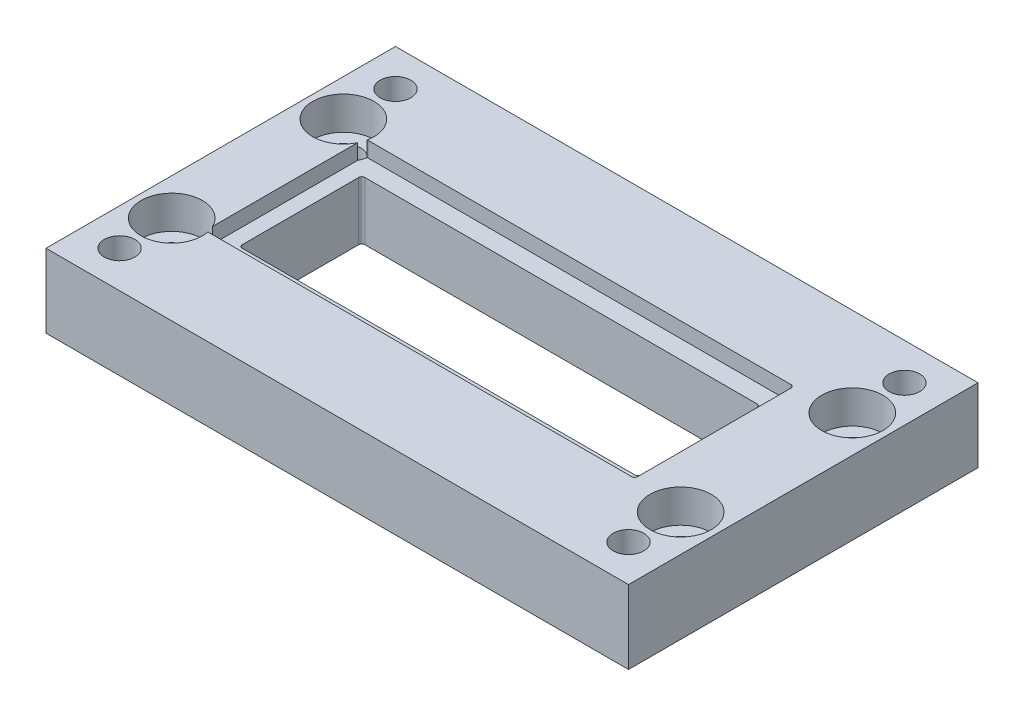
SolidWorks part; units mm, degrees
ref_plane "Front Plane" through (0, 0, 0) normal (0, 0, 1) x (1, 0, 0)
ref_plane "Top Plane" through (0, 0, 0) normal (0, 1, 0) x (1, 0, 0)
ref_plane "Right Plane" through (0, 0, 0) normal (1, 0, 0) x (0, 0, -1)
sketch "Sketch1" plane through (0, 0, 0) normal (0, 1, 0) x (1, 0, 0)
  line L0 (-56.5547, 0) -> (57.1484, 0) construction
  line L1 (47.5, 28.5) -> (-47.5, 28.5)
  line L2 (47.5, 28.5) -> (47.5, -28.5)
  line L3 (47.5, -28.5) -> (-47.5, -28.5)
  line L4 (-47.5, 28.5) -> (-47.5, -28.5)
  line L5 (47.5, 28.5) -> (-47.5, -28.5) construction
  line L6 (47.5, -28.5) -> (-47.5, 28.5) construction
  line L8 (30, -10) -> (-34, -10)
  line L9 (30.5, -9.5) -> (30.5, 9.5)
  line L10 (30, 10) -> (-34, 10)
  line L11 (-34.5, -9.5) -> (-34.5, 9.5)
  line L12 (30.5, -10) -> (-34.5, 10) construction
  line L13 (30.5, 10) -> (-34.5, -10) construction
  line L14 (32.5, 13) -> (-36.5, 13)
  line L15 (33, 12.5) -> (33, -12.5)
  line L16 (32.5, -13) -> (-36.5, -13)
  line L17 (-37, 12.5) -> (-37, -12.5)
  line L18 (33, 13) -> (-37, -13) construction
  line L19 (33, -13) -> (-37, 13) construction
  arc A0 (32.5, -13) -> (33, -12.5) centre (32.5, -12.5) ccw
  arc A1 (32.5, 13) -> (33, 12.5) centre (32.5, 12.5) cw
  arc A2 (-36.5, -13) -> (-37, -12.5) centre (-36.5, -12.5) cw
  arc A3 (-37, 12.5) -> (-36.5, 13) centre (-36.5, 12.5) cw
  arc A4 (-34, -10) -> (-34.5, -9.5) centre (-34, -9.5) cw
  arc A5 (-34, 10) -> (-34.5, 9.5) centre (-34, 9.5) ccw
  arc A6 (30.5, 9.5) -> (30, 10) centre (30, 9.5) ccw
  arc A7 (30, -10) -> (30.5, -9.5) centre (30, -9.5) ccw
  circle A8 centre (-41.5, -22.5) radius 2.058
  circle A9 centre (41.5, -22.5) radius 2.058
  circle A10 centre (-41.5, 22.5) radius 2.058
  circle A11 centre (41.5, 22.5) radius 2.058
  point P0 (0, 0)
  point P8 (-2, 0)
  point P15 (-2, 0)
  dimension "D9" = 0.5
  dimension "D10" = 0.5
  dimension "D11" = 6
  dimension "D13" = 45
  dimension "D1" = 95
  dimension "D2" = 57
  dimension "D3" = 65
  dimension "D4" = 20
  dimension "D5" = 13
  dimension "D6" = 3
  dimension "D7" = 2.5
  dimension "D8" = 26
  dimension "D12" = 83
  dimension "D14" = 6
extrude "Boss-Extrude2" add sketch "Sketch1" along normal blind 12 contours L1 L4 L3 L2 A11 A10 A9 A8 L17 A3 L14 A1 L15 A0 L16 A2 region at (46.3921, 0, 0)
extrude "Boss-Extrude3" add sketch "Sketch1<5>" along normal blind 9.5 contours A3 L17 A2 L16 A0 L15 A1 L14 A7 L8 A4 L11 A5 L10 A6 L9 region at (32.3255, 0, -12.3255)
sketch "Sketch1<5>" plane through (0, 0, 0) normal (0, 1, 0) x (1, 0, 0) same geometry as "Sketch1"
sketch "Sketch4" plane through (0, 12, 0) normal (0, 1, 0) x (1, 0, 0)
  line L0 (47.5, -28.5) -> (-47.5, -28.5) construction
  line L1 (-41.5, 14) -> (-41.5, -14) construction
  line L2 (41.5, 14) -> (41.5, -14) construction
  line L3 (-41.5, -14) -> (41.5, -14) construction
  line L4 (-41.5, -14) -> (-47.5, -14) construction
  line L5 (-47.5, 28.5) -> (-47.5, -28.5) construction
  line L6 (-41.5, 14) -> (41.5, 14) construction
  line L8 (47.5, 28.5) -> (47.5, -28.5) construction
  point P0 (-47.5, -14)
  dimension "D1" = 28
  dimension "D2" = 14.5
  dimension "D3" = 6
  dimension "D4" = 6
hole_wizard "CBORE for M6 Cheese Head Screw1" positions "3DSketch3" profile "Sketch7" counterbore size "M6" standard "DIN" end condition through all
sketch3d "3DSketch3"
  point P0 (-41.5, 12, -14)
  point P3 (41.5, 12, -14)
  point P6 (41.5, 12, 14)
  point P9 (-41.5, 12, 14)
sketch "Sketch7" plane through (-41.5, 12, -14) normal (1, 0, 0) x (0, 0, 1)
  line L0 (0, 0) -> (0, 12)
  line L1 (0, 12) -> (2.75, 12)
  line L3 (2.75, 12) -> (2.75, 5.4)
  line L4 (2.75, 5.4) -> (5, 5.4)
  line L5 (5, 5.4) -> (5, 0)
  line L7 (5, 0) -> (0, 0)
  line L11 (0, -6.35) -> (0, 107.95) construction
  dimension "Thru Hole Dia." = 5.5
  dimension "Thru Hole Depth" = 12
  dimension "C'Bore Dia." = 10
  dimension "C'Bore Depth" = 5.4
hole_wizard "Ø5.0 (5) Diameter Hole1" positions "3DSketch4" profile "Sketch8" hole size "Ø5.0" standard "DIN" end condition through all
sketch3d "3DSketch4"
  line L0 (-41.5, 12, -22.5) -> (-41.5, 0, -22.5) construction
  line L1 (41.5, 12, -22.5) -> (41.5, 0, -22.5) construction
  line L2 (41.5, 12, 22.5) -> (41.5, 0, 22.5) construction
  line L3 (-41.5, 12, 22.5) -> (-41.5, 0, 22.5) construction
  point P0 (-41.5, 12, -22.5)
  point P4 (41.5, 12, -22.5)
  point P8 (41.5, 12, 22.5)
  point P12 (-41.5, 12, 22.5)
sketch "Sketch8" plane through (-41.5, 12, -22.5) normal (1, 0, 0) x (0, 0, 1)
  line L0 (0, 0) -> (0, 12)
  line L1 (0, 12) -> (2.5, 12)
  line L2 (2.5, 12) -> (2.5, 0)
  line L5 (2.5, 0) -> (0, 0)
  line L11 (0, -6.35) -> (0, 107.95) construction
  dimension "Thru Hole Dia." = 5
  dimension "Thru Hole Depth" = 12
